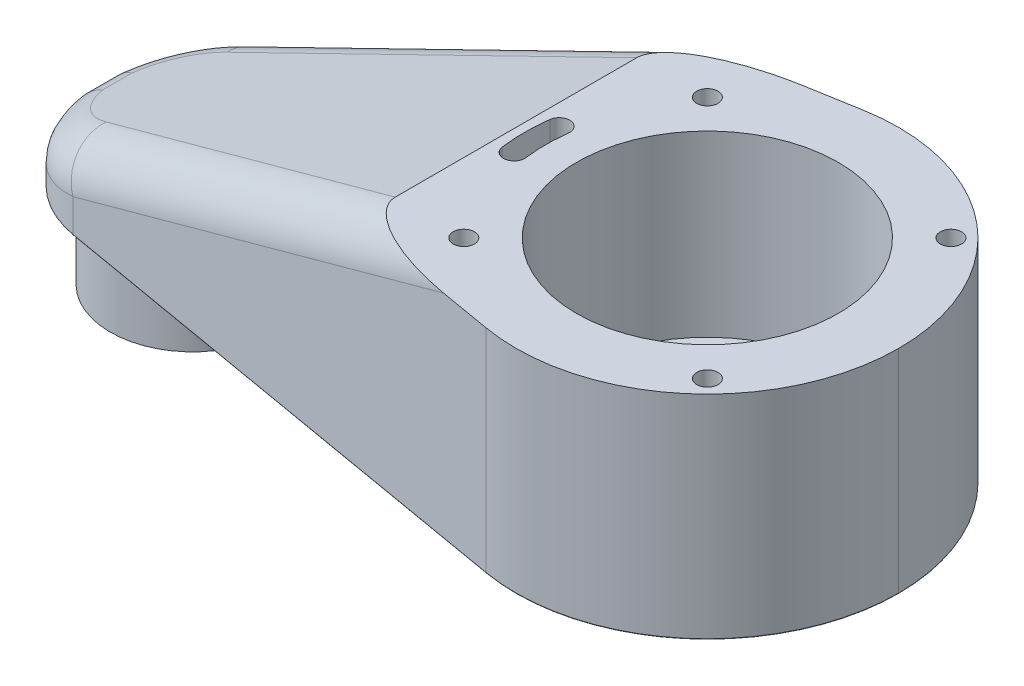
SolidWorks part; units mm, degrees
material "6061-T6 (SS)"
ref_plane "Front Plane" through (0, 0, 0) normal (0, 0, 1) x (1, 0, 0)
ref_plane "Top Plane" through (0, 0, 0) normal (0, 1, 0) x (1, 0, 0)
ref_plane "Right Plane" through (0, 0, 0) normal (1, 0, 0) x (0, 0, -1)
sketch "Sketch1" plane through (0, 0, 0) normal (0, 1, 0) x (1, 0, 0)
  line L1 (0, 0) -> (120.65, 0)
  line L2 (0, 0) -> (0, 57.15)
  line L3 (0, 57.15) -> (120.65, 57.15)
  line L4 (120.65, 0) -> (120.65, 57.15)
  dimension "D1" = 120.65
  dimension "D2" = 57.15
extrude "Boss-Extrude1" add sketch "Sketch1" along normal blind 31.75
sketch "Sketch2" plane through (0, 31.75, 0) normal (0, 1, 0) x (1, 0, 0)
  line L0 (120.65, 28.575) -> (92.075, 28.575) construction
  line L1 (120.65, 0) -> (120.65, 57.15) construction
  circle A0 centre (92.075, 28.575) radius 19.55
  dimension "D2" = 39.1
  dimension "D1" = 28.575
extrude "Cut-Extrude1" cut sketch "Sketch2" against normal blind 26.67
fillet "Fillet1" radius 28.575 2 edges at (120.65, 15.875, -57.15) (120.65, 15.875, 0)
sketch "Sketch3" plane through (0, 5.08, 0) normal (0, 1, 0) x (1, 0, 0)
  line L0 (90.0607, 29.845) -> (94.0893, 29.845)
  arc A0 (90.0607, 29.845) -> (94.0893, 29.845) centre (92.075, 28.575) ccw
  dimension "D1" = 4.7625
  dimension "D2" = 1.27
extrude "Cut-Extrude2" cut sketch "Sketch3" against normal through all
sketch "Sketch4" plane through (0, 0, 0) normal (0, -1, 0) x (-1, 0, 0)
  line L0 (0, 57.15) -> (0, 0) construction
  circle A0 centre (-15.24, 28.575) radius 12.325
  circle A1 centre (-15.24, 28.575) radius 9.785
  dimension "D2" = 24.65
  dimension "D3" = 2.54
  dimension "D1" = 15.24
extrude "Boss-Extrude2" add sketch "Sketch4" along normal blind 12.7
sketch "Sketch5" plane through (0, 31.75, 0) normal (0, 1, 0) x (1, 0, 0)
  line L0 (92.075, 28.575) -> (148.9411, 28.575) construction
  line L1 (92.075, 28.575) -> (110.26, 10.39) construction
  circle A0 centre (92.075, 28.575) radius 25.7175 construction
  circle A1 centre (110.26, 10.39) radius 1.5875
  dimension "D1" = 51.435
  dimension "D3" = 3.175
  dimension "D2" = 45
extrude "Cut-Extrude3" cut sketch "Sketch5" against normal blind 25.4
pattern_circular "CirPattern1" count 4 over 360 about axis through (92.075, 0, -28.575) along (0, 1, 0) of "Cut-Extrude3"
sketch "Sketch6" plane through (0, 0, 0) normal (0, -1, 0) x (1, 0, 0)
  line L0 (87.2124, -56.7332) -> (12.6024, -43.8489)
  line L1 (87.2124, -0.4168) -> (12.6024, -13.3011)
  line L2 (92.075, 0) -> (0, 0)
  line L3 (0, 0) -> (0, -25.7479)
  line L4 (0, -57.15) -> (92.075, -57.15)
  line L5 (0, -31.4021) -> (0, -57.15)
  arc A0 (92.075, 0) -> (87.2124, -0.4168) centre (92.075, -28.575) ccw
  arc A1 (12.6024, -13.3011) -> (0, -25.7479) centre (15.24, -28.575) ccw
  circle A2 centre (15.24, -28.575) radius 12.325 construction
  arc A3 (87.2124, -56.7332) -> (92.075, -57.15) centre (92.075, -28.575) ccw
  arc A4 (0, -31.4021) -> (12.6024, -43.8489) centre (15.24, -28.575) ccw
  dimension "D1" = 3.175
extrude "Cut-Extrude4" cut sketch "Sketch6" against normal through all
ref_plane "Plane1" through (0, 0, -28.575) normal (0, 0, -1) x (-1, 0, 0)
sketch "Sketch8" plane through (0, 0, -28.575) normal (0, 0, -1) x (-1, 0, 0)
  line L0 (0, 6.35) -> (-63.5, 31.75)
  line L1 (-63.5, 31.75) -> (0, 31.75)
  line L2 (0, 31.75) -> (0, 6.35)
  line L3 (-12.6024, 0) -> (0, 0) construction
  line L5 (0, 31.75) -> (0, 0) construction
  line L6 (0, 31.75) -> (-12.6024, 31.75) construction
  dimension "D1" = 6.35
  dimension "D2" = 63.5
  dimension "D3" = 0
  dimension "D4" = 0
extrude "Cut-Extrude5" cut sketch "Sketch8" against normal through all and the other way through all
fillet "Fillet2" radius 6.35 5 edges at (4.3481, 8.0892, -39.603) (4.3481, 8.0892, -17.547) (0, 6.35, -28.575) (38.0512, 21.5705, -48.2436) (38.0512, 21.5705, -8.9064)
fillet "Fillet3" radius 0.127 6 edges at (4.3481, 0, -17.547) (4.3481, 0, -39.603) (49.9074, 0, -50.2911) (110.4813, 0, -50.4323) (110.4813, 0, -6.7177) (49.9074, 0, -6.8589)
sketch "Sketch9" plane through (0, 31.75, 0) normal (0, 1, 0) x (1, 0, 0)
  line L0 (92.075, 28.575) -> (33.7556, 28.575) construction
  line L1 (92.075, 28.575) -> (66.5775, 25.2182) construction
  line L2 (92.075, 28.575) -> (66.5775, 31.9318) construction
  circle A0 centre (92.075, 28.575) radius 25.7175 construction
  arc A1 (65.0036, 25.011) -> (68.1514, 25.4254) centre (66.5775, 25.2182) ccw
  arc A2 (68.1514, 31.7246) -> (65.0036, 32.139) centre (66.5775, 31.9318) ccw
  arc A3 (65.0036, 32.139) -> (65.0036, 25.011) centre (92.075, 28.575) ccw
  arc A4 (68.1514, 31.7246) -> (68.1514, 25.4254) centre (92.075, 28.575) ccw
  dimension "D3" = 3.175
  dimension "D1" = 15
  dimension "D2" = 7.5
extrude "Cut-Extrude6" cut sketch "Sketch9" against normal through all
sketch "Sketch10" plane through (0, 0, 0) normal (0, -1, 0) x (1, 0, 0)
  line L0 (0, 0) -> (123.9165, 0) construction
  line L1 (66.7847, -23.6443) -> (15.24, -23.6443)
  line L2 (66.7847, -33.5057) -> (15.24, -33.5057)
  line L3 (66.7847, -23.6443) -> (66.7847, -33.5057)
  arc A0 (68.1514, -25.4254) -> (65.0036, -25.011) centre (66.5775, -25.2182) ccw construction
  arc A1 (65.0036, -32.139) -> (68.1514, -31.7246) centre (66.5775, -31.9318) ccw construction
  arc A2 (15.24, -23.6443) -> (15.24, -33.5057) centre (15.24, -28.575) ccw
  dimension "D1" = 0
  dimension "D2" = 0
extrude "Cut-Extrude7" cut sketch "Sketch10" against normal blind 5.08 and the other way through all
fillet "Fillet4" radius 3.81 3 edges at (40.8052, 5.08, -33.5057) (10.3093, 5.08, -28.575) (40.8052, 5.08, -23.6443)
fillet "Fillet5" radius 1.27 2 edges at (26.5357, -6.35, -33.5057) (26.5357, -6.35, -23.6443)
equation "\"D2@Sketch9\"=\"D1@Sketch9\"/2"
